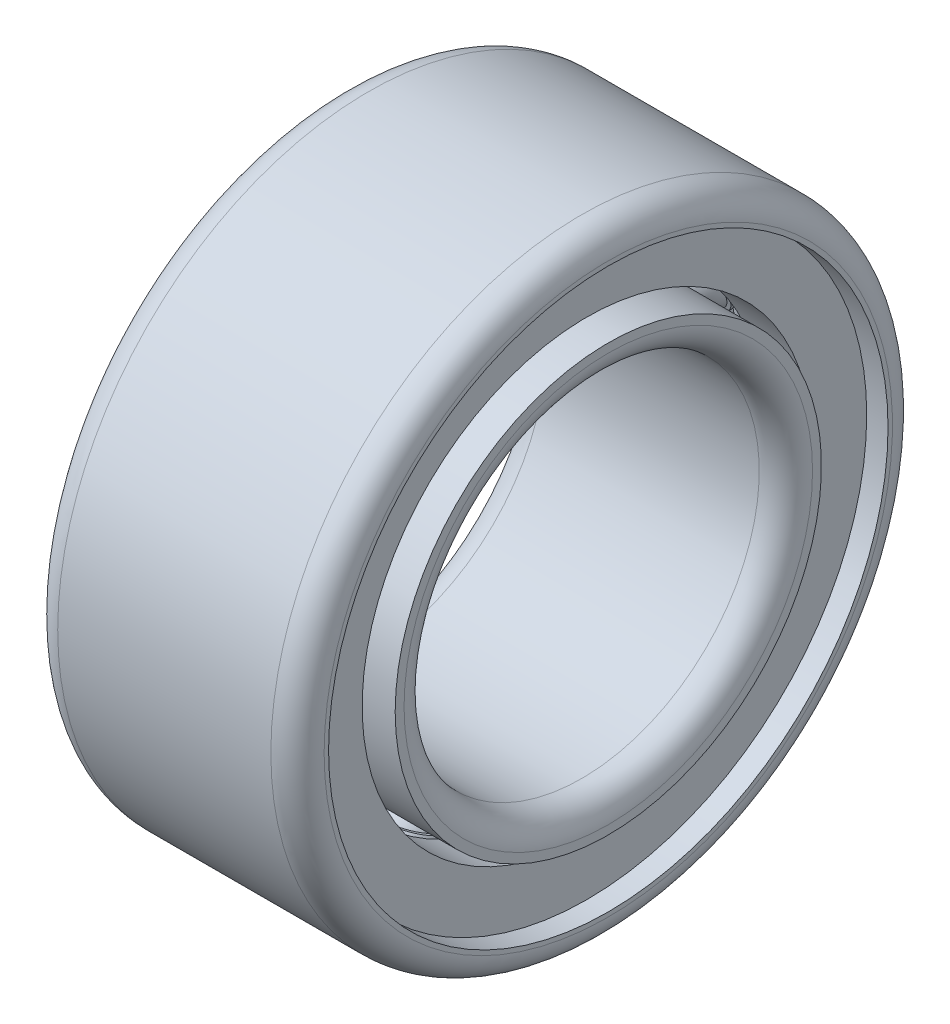
SolidWorks part; units mm, degrees
revolve "凸台-旋转2" add sketch "草图6" angle 360 about L4
sketch "草图6" plane through (0, 0, 0) normal (0, 0, 1) x (1, 0, 0)
  line L0 (0, 0) -> (5.5439, 0) construction
  line L1 (-12.4206, 0) -> (9.8128, 0) construction
  line L2 (0, 0) -> (0, 11.4011) construction
  line L3 (-5.5681, 2.775) -> (6.1049, 2.775) construction
  line L4 (-5.5681, 2.775) -> (6.1049, 2.775) construction
  line L5 (-0.4, 2.775) -> (0.4, 2.775)
  arc A0 (-0.4, 2.775) -> (0.4, 2.775) centre (0, 2.775) ccw
  dimension "Dw" = 0.8
revolve "基体-旋转" add sketch "草图2" angle 360 about L0
sketch "草图2" plane through (0, 0, 0) normal (0, 0, 1) x (1, 0, 0)
  line L0 (-12.4206, 0) -> (9.8128, 0) construction
  line L1 (0, 0) -> (0, 37.3563) construction
  line L2 (-5.5681, 2.775) -> (6.1049, 2.775) construction
  line L3 (-0.088, 2.885) -> (0.088, 2.885)
  line L4 (-0.088, 2.885) -> (-0.088, 2.665)
  line L5 (-0.088, 2.665) -> (0.088, 2.665)
  line L6 (0.088, 2.885) -> (0.088, 2.665)
  dimension "D1" = 0.176
  dimension "D2" = 0.088
  dimension "D3" = 0.22
  dimension "D4" = 0.11
  dimension "D5" = 2.775
revolve "凸台-旋转1" add sketch "草图3" angle 360 about L1
sketch "草图3" plane through (0, 0, 0) normal (0, 0, 1) x (1, 0, 0)
  line L0 (-5.5681, 2.775) -> (6.1049, 2.775) construction
  line L1 (-5.5681, 2.775) -> (6.1049, 2.775) construction
  line L2 (-12.4206, 0) -> (9.8128, 0) construction
  line L3 (-12.4206, 0) -> (9.8128, 0) construction
  line L4 (0, 0) -> (0, 37.3563) construction
  line L5 (0, 0) -> (0, 37.3563) construction
  line L6 (-0.44, 2.775) -> (0.44, 2.775)
  arc A0 (-0.44, 2.775) -> (0.44, 2.775) centre (0, 2.775) ccw
  dimension "Dwww" = 0.88
  dimension "D2" = 0.44
pattern_circular "阵列(圆周)1" count 11 over 360 about axis through (-12.4206, 0, 0) along (1, 0, 0) of "凸台-旋转1"
revolve "凸台-旋转3" add sketch "草图7" angle 360 about L0
sketch "草图7" plane through (0, 0, 0) normal (0, 0, 1) x (1, 0, 0)
  line L0 (0, 0) -> (6.6488, 0) construction
  line L1 (0, 0) -> (0, 16.8954) construction
  line L2 (-1.2, 3.5) -> (1.2, 3.5)
  line L3 (-1.5, 3.2) -> (-1.5, 3.15)
  line L4 (-1.5, 3.15) -> (-0.1071, 3.15)
  line L5 (1.5, 3.2) -> (1.5, 3.15)
  line L6 (0.1071, 3.15) -> (0.7248, 3.15)
  line L7 (1.26, 3.15) -> (1.5, 3.15)
  line L8 (0.7248, 3.1) -> (1.26, 3.1)
  line L9 (0.7248, 3.1) -> (0.7248, 3.15)
  line L11 (1.26, 3.1) -> (1.26, 3.15)
  arc A0 (-1.2, 3.5) -> (-1.5, 3.2) centre (-1.2, 3.2) ccw
  arc A1 (1.2, 3.5) -> (1.5, 3.2) centre (1.2, 3.2) cw
  arc A2 (0.3846, 2.885) -> (-0.3846, 2.885) centre (0, 2.775) ccw construction
  arc A3 (0.1392, 3.15) -> (0, 3.175) centre (0, 2.775) ccw construction
  arc A4 (0.1071, 3.15) -> (-0.1071, 3.15) centre (0, 2.775) ccw
  point P10 (-1.5, 3.5)
  point P13 (1.5, 3.5)
  dimension "D3" = 1.5
  dimension "D4" = 0.5352
  dimension "D5" = 6.2
  dimension "D6" = 0.24
  dimension "B" = 3
ref_plane "基准面1" through (0, 0, 0) normal (0, 0, 1) x (1, 0, 0)
ref_plane "基准面2" through (0, 0, 0) normal (0, 1, 0) x (1, 0, 0)
ref_plane "基准面3" through (0, 0, 0) normal (1, 0, 0) x (0, 0, -1)
sketch "尺寸草图" plane through (0, 0, 0) normal (0, 0, 1) x (1, 0, 0)
  point P0 (0, -75.4307)
  point P1 (0.8, -75.4307)
  point P2 (0, 50.7088)
  point P3 (4, 50.7088)
  point P4 (7, 50.7088)
  point P5 (3, 50.7088)
  point P6 (0, -10.9899)
  point P7 (4.8, -10.9899)
  point P8 (6.2, -10.9899)
  point P9 (0.3, -10.9899)
  point P10 (11, -75.4307)
  dimension "B" = 3
sketch "草图4" plane through (0, 0, 0) normal (0, 0, 1) x (1, 0, 0)
  line L0 (0, 0) -> (8.1272, 0) construction
  line L1 (-12.4206, 0) -> (9.8128, 0) construction
  line L3 (-0.088, 2.885) -> (0.088, 2.885) construction
  line L4 (-0.44, 3.325) -> (0.44, 3.325)
  line L5 (-0.44, 3.325) -> (-0.44, 2.885)
  line L6 (-0.44, 2.885) -> (0.44, 2.885)
  line L7 (0.44, 3.325) -> (0.44, 2.885)
revolve "切除-旋转1" cut sketch "草图4" angle 360 about L0
sketch "草图5" plane through (0, 0, 0) normal (0, 0, 1) x (1, 0, 0)
  line L0 (0, 0) -> (8.2665, 0) construction
  line L1 (-12.4206, 0) -> (9.8128, 0) construction
  line L2 (-0.088, 2.665) -> (0.088, 2.665) construction
  line L3 (-0.44, 2.665) -> (0.44, 2.665)
  line L4 (-0.44, 2.665) -> (-0.44, 2.225)
  line L5 (-0.44, 2.225) -> (0.44, 2.225)
  line L6 (0.44, 2.665) -> (0.44, 2.225)
revolve "切除-旋转2" cut sketch "草图5" angle 360 about L0
pattern_circular "阵列(圆周)2" count 11 over 360 about axis through (-12.4206, 0, 0) along (1, 0, 0) of "凸台-旋转2"
sketch "草图8" plane through (0, 0, 0) normal (0, 0, 1) x (1, 0, 0)
  line L0 (-12.4206, 0) -> (9.8128, 0) construction
  line L1 (-12.4206, 0) -> (9.8128, 0) construction
  line L2 (1.5, 3.2) -> (1.5, 3.15) construction
  line L3 (-1.5, 2.4) -> (-0.1071, 2.4)
  line L4 (-1.5, 2.4) -> (-1.5, 2.3)
  line L5 (-1.2, 2) -> (1.2, 2)
  line L6 (1.5, 2.4) -> (1.5, 2.3)
  line L7 (-1.5, 3.2) -> (-1.5, 3.15) construction
  line L8 (0.1071, 2.4) -> (1.5, 2.4)
  arc A0 (-1.5, 2.3) -> (-1.2, 2) centre (-1.2, 2.3) ccw
  arc A1 (1.2, 2) -> (1.5, 2.3) centre (1.2, 2.3) ccw
  arc A2 (-0.3846, 2.665) -> (0.3846, 2.665) centre (0, 2.775) ccw construction
  arc A3 (-0.3846, 2.665) -> (0.3846, 2.665) centre (0, 2.775) ccw construction
  arc A4 (-0.1071, 2.4) -> (0.1071, 2.4) centre (0, 2.775) ccw
  dimension "D1" = 0.3
  dimension "DD" = 4
  dimension "D2" = 0.01
revolve "凸台-旋转4" add sketch "草图8" angle 360 about L1
sketch "草图10" plane through (0, 0, 0) normal (0, 0, 1) x (1, 0, 0)
  line L0 (0.7248, 3.15) -> (0.7248, -3.15) construction
  line L1 (1.26, 3.1) -> (0.7248, 3.1)
  line L2 (1.26, 3.1) -> (1.26, 2.532)
  line L3 (1.26, 2.532) -> (0.7248, 2.532)
  line L4 (0.7248, 3.1) -> (0.7248, 2.532)
  line L5 (0.1071, 2.4) -> (1.5, 2.4) construction
  line L6 (0, 0) -> (-5.3515, 0) construction
  line L7 (-12.4206, 0) -> (9.8128, 0) construction
  dimension "D1" = 0.132
revolve "凸台-旋转5" add sketch "草图10" angle 360 about L6
sketch "草图11" plane through (0, 0, 0) normal (1, 0, 0) x (0, 0, -1)
  circle A0 centre (0, 0) radius 3.5
  circle A1 centre (0, 0) radius 3.5 construction
extrude "切除-拉伸1" cut sketch "草图11" against normal blind 10
mirror "镜向所有1" about plane through (0, 0, 0) normal (1, 0, 0) of bodies 109
equation "\"D5@草图7\" = \"防尘圈径D3@尺寸草图\""
equation "\"Z@阵列(圆周)1\"=\"球数Z@尺寸草图\" "
equation "\"Dw@草图6\"=\"球径DW@尺寸草图\""
equation "\"DD@草图8\"=\"d@尺寸草图\""
equation "\"D@草图7\"=\"DD@尺寸草图\""
equation "\"B@草图7\"=\"B@尺寸草图\" "
equation "\"DD2@草图8\"=\"内圈外径DD2@尺寸草图\""
equation "\"R@草图7\"=\"r@尺寸草图\""
equation "\"D3@草图2\" = 0.25*\"Dwww@草图3\""
equation "\"D4@草图2\" = \"D3@草图2\"/2"
equation "\"Dwww@草图3\" = 1.1*\"Dw@草图6\""
equation "\"D2@草图3\" = 0.5*\"Dwww@草图3\""
equation "\"D1@草图2\" = 0.2*\"Dwww@草图3\""
equation "\"D2@草图2\" = 0.5*\"D1@草图2\""
equation "\"切除位置@草图4\" = \"Dwww@草图3\"/2"
equation "\"D1@阵列(圆周)2\" = \"Z@阵列(圆周)1\""
equation "\"D3@草图7\" = \"B@草图7\" / 2"
equation "\"D1@草图8\" = \"R@草图7\""
equation "\"D2@草图7\" = 0.9*\"D@草图7\""
equation "\"D5@草图2\" = 0.25* ( \"D2@草图7\" + \"DD2@草图8\" )  "
equation "\"D6@草图7\" = 0.08 * \"B@草图7\""
equation "\"D1@草图10\" = 0.15*\"Dwww@草图3\""
